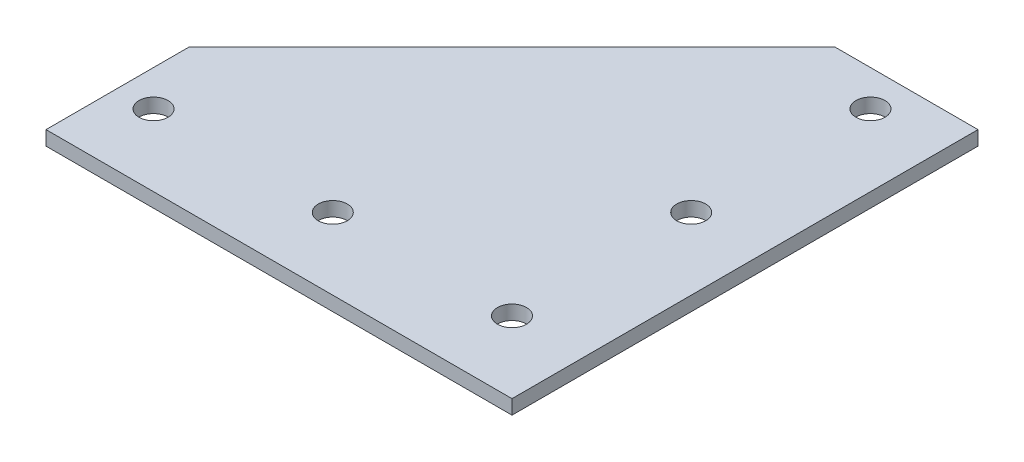
SolidWorks part; units mm, degrees
material "6061-T6 (SS)"
ref_plane "Front Plane" through (0, 0, 0) normal (0, 0, 1) x (1, 0, 0)
ref_plane "Top Plane" through (0, 0, 0) normal (0, 1, 0) x (1, 0, 0)
ref_plane "Right Plane" through (0, 0, 0) normal (1, 0, 0) x (0, 0, -1)
sketch "Sketch1" plane through (0, 0, 0) normal (0, 1, 0) x (1, 0, 0)
  line L0 (0, 0) -> (-100, 0) construction
  line L1 (0, 0) -> (0, 100) construction
  line L2 (20, -20) -> (-110, -20)
  line L3 (20, -20) -> (20, 110)
  line L4 (-110, -20) -> (-110, 20)
  line L5 (-110, 20) -> (-20, 110)
  line L6 (-20, 110) -> (20, 110)
  circle A0 centre (-100, 0) radius 4.05
  circle A1 centre (-50, 0) radius 4.05
  circle A2 centre (0, 0) radius 4.05
  circle A3 centre (0, 100) radius 4.05
  circle A4 centre (0, 50) radius 4.05
  dimension "D1" = 8.1
  dimension "D2" = 100
  dimension "D3" = 20
  dimension "D4" = 20
  dimension "D5" = 40
  dimension "D6" = 10
extrude "Boss-Extrude1" add sketch "Sketch1" along normal blind 4
